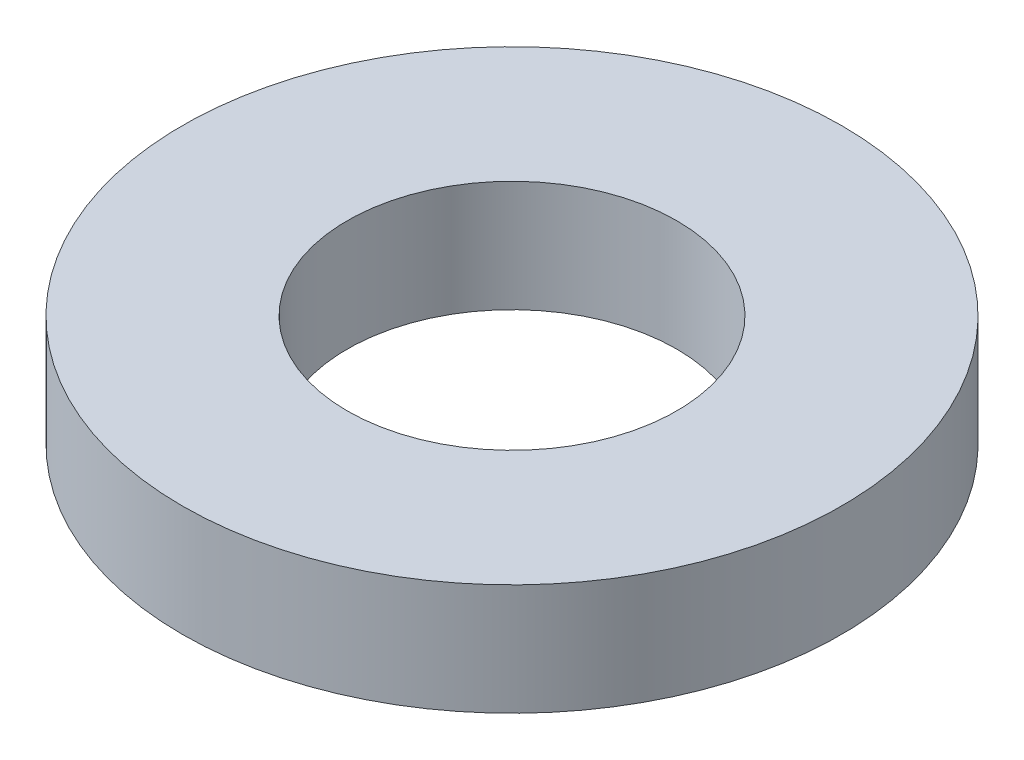
SolidWorks part; units mm, degrees
ref_plane "Front Plane" through (0, 0, 0) normal (0, 0, 1) x (1, 0, 0)
ref_plane "Top Plane" through (0, 0, 0) normal (0, 1, 0) x (1, 0, 0)
ref_plane "Right Plane" through (0, 0, 0) normal (1, 0, 0) x (0, 0, -1)
sketch "Sketch1" plane through (0, 0, 0) normal (0, 1, 0) x (1, 0, 0)
  circle A0 centre (0, 0) radius 80
  dimension "FLANGE_OD" = 160
extrude "Boss-Extrude1" add sketch "Sketch1" along normal blind 27
sketch "Sketch2" plane through (0, 0, 0) normal (0, 1, 0) x (1, 0, 0)
  circle A0 centre (0, 0) radius 40
  dimension "BORE_D" = 80
extrude "Cut-Extrude1" cut sketch "Sketch2" along normal through all
sketch "Sketch3" plane through (0, 27, 0) normal (0, 1, 0) x (1, 0, 0)
  circle A0 centre (0, 0) radius 33.8752 construction
  circle A1 centre (-33.8752, 0) radius 2.1984
  dimension "BOLT_D" = 4.3968
  dimension "BOLT_PCD" = 67.7503
extrude "Cut-Extrude2" cut sketch "Sketch3" against normal blind 17.0847 rebuild error yes
pattern_circular "CirPattern1" count 8 over 360 rebuild error yes
